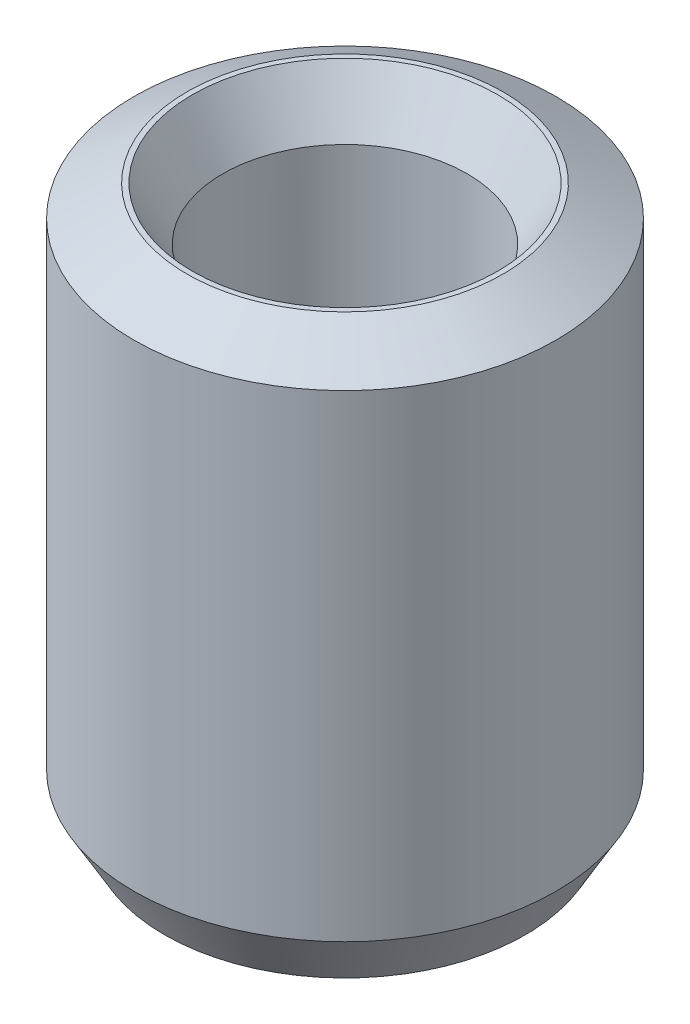
SolidWorks part; units mm, degrees
ref_plane "Front Plane" through (0, 0, 0) normal (0, 0, 1) x (1, 0, 0)
ref_plane "Top Plane" through (0, 0, 0) normal (0, 1, 0) x (1, 0, 0)
ref_plane "Right Plane" through (0, 0, 0) normal (1, 0, 0) x (0, 0, -1)
sketch "Sketch1" plane through (0, 0, 0) normal (0, 1, 0) x (1, 0, 0)
  circle A0 centre (0, 0) radius 22.5
  dimension "SLEEVE_OD" = 45
extrude "Boss-Extrude1" add sketch "Sketch1" along normal blind 59.8109
sketch "Sketch2" plane through (0, 0, 0) normal (0, 1, 0) x (1, 0, 0)
  circle A0 centre (0, 0) radius 13.0244
  dimension "BORE_D" = 26.0489
extrude "Cut-Extrude1" cut sketch "Sketch2" along normal through all
chamfer "Chamfer1" distance 3.2658 angle 60 4 edges at (0, 59.8109, 13.0244) (0, 0, 13.0244) (0, 0, 22.5) (0, 59.8109, 22.5) first distance on face at (0, 59.8109, 13.0244) first distance on face at (0, 0, 13.0244) first distance on face at (0, 59.8109, 22.5)
